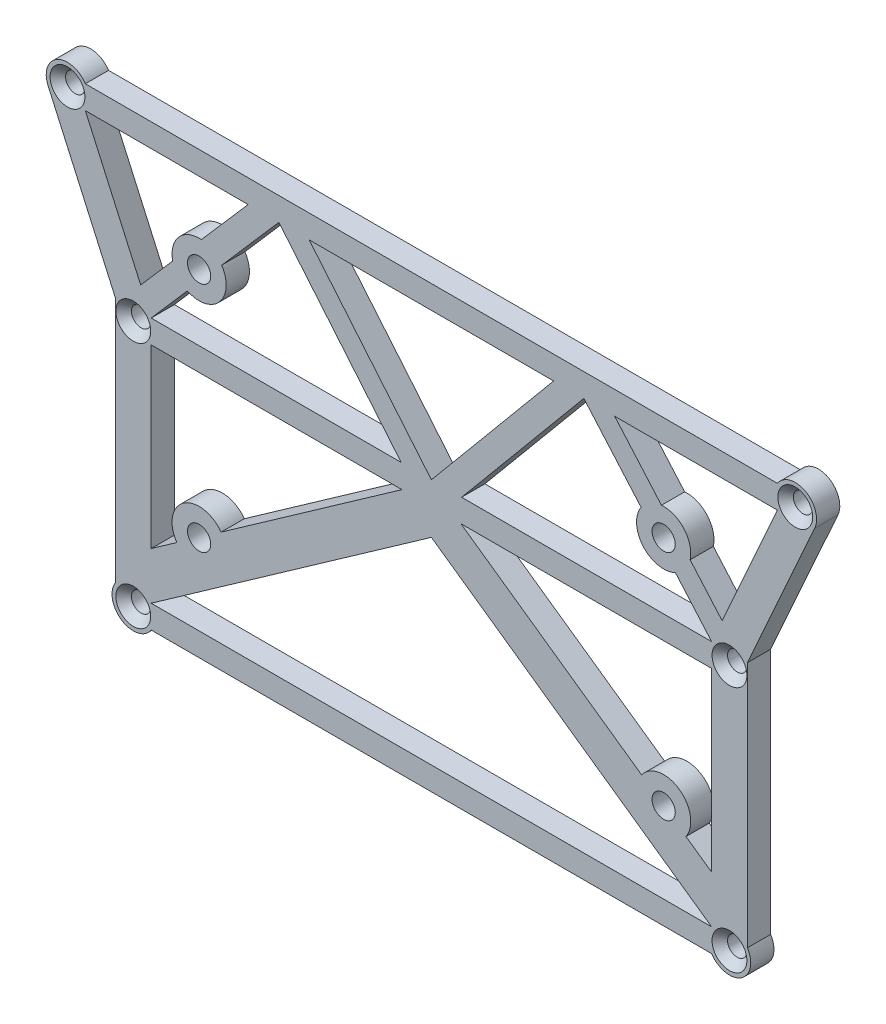
SolidWorks part; units mm, degrees
ref_plane "Front Plane" through (0, 0, 0) normal (0, 0, 1) x (1, 0, 0)
ref_plane "Top Plane" through (0, 0, 0) normal (0, 1, 0) x (1, 0, 0)
ref_plane "Right Plane" through (0, 0, 0) normal (1, 0, 0) x (0, 0, -1)
sketch "Sketch1" plane through (0, 0, 0) normal (0, 0, 1) x (1, 0, 0)
  line L0 (8.5, 31.9015) -> (85.5, 31.9015) construction
  line L1 (0, 0) -> (94, 0) construction
  line L2 (0, 0) -> (0, 53.8533) construction
  line L3 (0, 53.8533) -> (94, 53.8533) construction
  line L5 (94, 53.8533) -> (85.5, 0) construction
  line L6 (94, 53.8533) -> (85.5, 31.9015) construction
  line L7 (8.5, 31.9015) -> (8.5, 0) construction
  line L8 (8.5, 0) -> (85.5, 0) construction
  line L9 (85.5, 31.9015) -> (85.5, 0) construction
  line L10 (47, 55.3533) -> (47, -1.5) construction
  line L11 (0, 53.8533) -> (8.5, 31.9015) construction
  line L12 (0, 53.8533) -> (8.5, 0) construction
  line L14 (6.1738, 33.3682) -> (-2.5092, 52.7279)
  line L15 (2.3049, 55.3533) -> (91.6951, 55.3533)
  line L16 (9.4525, 36.4169) -> (2.3049, 52.3533)
  line L17 (10.8049, 33.4015) -> (43.0952, 33.4015)
  line L18 (10.8049, 30.4015) -> (43.1967, 30.4015)
  line L19 (10.8049, 30.4015) -> (10.8049, 7.6134)
  line L20 (10.8049, 1.5) -> (83.1951, 1.5)
  line L21 (10.8049, -1.5) -> (83.1951, -1.5)
  line L22 (2.3049, 52.3533) -> (23.3272, 52.3533)
  line L23 (6.1738, 1.4667) -> (6.1738, 33.3682)
  line L24 (94, 0) -> (94, 53.8533) construction
  line L25 (87.8262, 1.4667) -> (87.8262, 33.3682)
  line L26 (83.1951, 30.4015) -> (83.1951, 7.6134)
  line L27 (84.5475, 36.4169) -> (91.6951, 52.3533)
  line L28 (87.8262, 33.3682) -> (96.5092, 52.7279)
  line L29 (10.8049, 33.4015) -> (27.3049, 52.3533)
  line L30 (27.3049, 52.3533) -> (43.0952, 33.4015)
  line L31 (47, 33.4015) -> (31.2097, 52.3533)
  line L32 (9.4525, 36.4169) -> (23.3272, 52.3533)
  line L33 (31.2097, 52.3533) -> (62.7903, 52.3533)
  line L34 (50.9048, 33.4015) -> (83.1951, 33.4015)
  line L35 (10.8049, 1.5) -> (47, 26.9638)
  line L36 (10.8049, 7.6134) -> (43.1967, 30.4015)
  line L37 (50.8033, 30.4015) -> (83.1951, 30.4015)
  line L38 (83.1951, 7.6134) -> (50.8033, 30.4015)
  line L39 (83.1951, 1.5) -> (47, 26.9638)
  line L40 (47, 33.4015) -> (62.7903, 52.3533)
  line L41 (66.6951, 52.3533) -> (50.9048, 33.4015)
  line L42 (84.5475, 36.4169) -> (70.6728, 52.3533)
  line L43 (83.1951, 33.4015) -> (66.6951, 52.3533)
  line L44 (70.6728, 52.3533) -> (91.6951, 52.3533)
  circle A0 centre (0, 53.8533) radius 1.25
  circle A2 centre (8.5, 31.9015) radius 1.25
  circle A4 centre (8.5, 0) radius 1.25
  arc A9 (6.1738, 1.4667) -> (10.8049, -1.5) centre (8.5, 0) ccw
  arc A10 (2.3049, 55.3533) -> (-2.5092, 52.7279) centre (0, 53.8533) ccw
  circle A11 centre (8.5, 0) radius 2.75 construction
  circle A12 centre (8.5, 31.9015) radius 2.75 construction
  circle A13 centre (0, 53.8533) radius 2.75 construction
  circle A14 centre (94, 53.8533) radius 2.75 construction
  circle A15 centre (85.5, 31.9015) radius 2.75 construction
  circle A16 centre (85.5, 0) radius 2.75 construction
  arc A17 (91.6951, 55.3533) -> (96.5092, 52.7279) centre (94, 53.8533) cw
  arc A18 (87.8262, 1.4667) -> (83.1951, -1.5) centre (85.5, 0) cw
  circle A19 centre (85.5, 0) radius 1.25
  circle A20 centre (85.5, 31.9015) radius 1.25
  circle A21 centre (94, 53.8533) radius 1.25
  point P9 (47, 53.8533)
  point P28 (47, 0)
  point P29 (47, 31.9015)
  point P37 (47, 55.2859)
  point P39 (0, 0)
  point P40 (0, 0)
  point P41 (0, 0)
  point P42 (0, 0)
  point P47 (47, 52.3533)
  point P50 (47, 1.5)
  point P51 (47, 1.5)
  point P53 (47, 26.9638)
  point P55 (47, 33.4015)
  point P58 (47, 30.5)
  point P59 (47, 33.5)
  point P60 (47, 52.2859)
  point P73 (47, 26.9638)
  dimension "D7" = 2.5
  dimension "D8" = 3
  dimension "D9" = 5.5
  dimension "D16" = 2.75
  dimension "D18" = 3
  dimension "D2" = 38.5
  dimension "D3" = 47
  dimension "D4" = 56.8533
  dimension "D5" = 23.54
  dimension "D6" = 54.52
  dimension "D10" = 3
  dimension "D11" = 3
  dimension "D12" = 3
  dimension "D13" = 1.5
  dimension "D14" = 1.5
  dimension "D15" = 1.5
  dimension "D17" = 1.1254
  dimension "D19" = 5
  dimension "D20" = 25
  dimension "D21" = 77
  dimension "D22" = 31.9015
extrude "Boss-Extrude1" add sketch "Sketch1" along normal blind 3
chamfer "Chamfer1" distance 1 angle 45 6 edges at (9.75, 0, 3) (9.75, 31.9015, 3) (1.25, 53.8533, 3) (92.75, 53.8533, 3) (84.25, 31.9015, 3) (84.25, 0, 3)
sketch "Sketch2" plane through (0, 0, 3) normal (0, 0, 1) x (1, 0, 0)
  line L0 (47, 55.3533) -> (47, -1.5) construction
  line L1 (17, 41.9267) -> (77, 41.9267) construction
  line L2 (17, 41.9267) -> (17, 11.9267) construction
  line L3 (17, 11.9267) -> (77, 11.9267) construction
  line L4 (77, 41.9267) -> (77, 11.9267) construction
  line L5 (17, 41.9267) -> (77, 11.9267) construction
  line L6 (17, 11.9267) -> (77, 41.9267) construction
  line L7 (10.8049, -1.5) -> (83.1951, -1.5) construction
  line L8 (91.6951, 55.3533) -> (2.3049, 55.3533) construction
  circle A0 centre (17, 41.9267) radius 3.5
  circle A1 centre (17, 11.9267) radius 3.5
  circle A2 centre (17, 11.9267) radius 1.5
  circle A3 centre (17, 41.9267) radius 1.5
  circle A4 centre (77, 41.9267) radius 1.5
  circle A5 centre (77, 41.9267) radius 3.5
  circle A6 centre (77, 11.9267) radius 1.5
  circle A7 centre (77, 11.9267) radius 3.5
  point P4 (0, 0)
  point P14 (0, 0)
  point P15 (47, 26.9267)
  point P19 (47, 41.9267)
  line M16 (83.1951, 1.5) -> (10.8049, 1.5)
  line M18 (10.8049, 30.4015) -> (43.1967, 30.4015)
  dimension "D2" = 3
  dimension "D3" = 7
  dimension "D4" = 60
  dimension "D5" = 30
  dimension "D1" = 0
extrude "Boss-Extrude2" add sketch "Sketch2" against normal up to surface (3 mm away) contours A1 | A7 | A0 | A5 up to face at (72.3979, 22.8055, 0)
extrude "Cut-Extrude1" cut sketch "Sketch2<3>" against normal blind 3 contours A2 M16 | A2 M16 | A3 M18 | A3 M18 | A4 M18 | A4 M18 | A6 M16 | A6 M16 region at (17, 11.9267, 3) region at (17, 41.9267, 3) region at (77, 41.9267, 3) region at (77, 11.9267, 3)
sketch "Sketch2<3>" plane through (0, 0, 3) normal (0, 0, 1) x (1, 0, 0) same geometry as "Sketch2"
